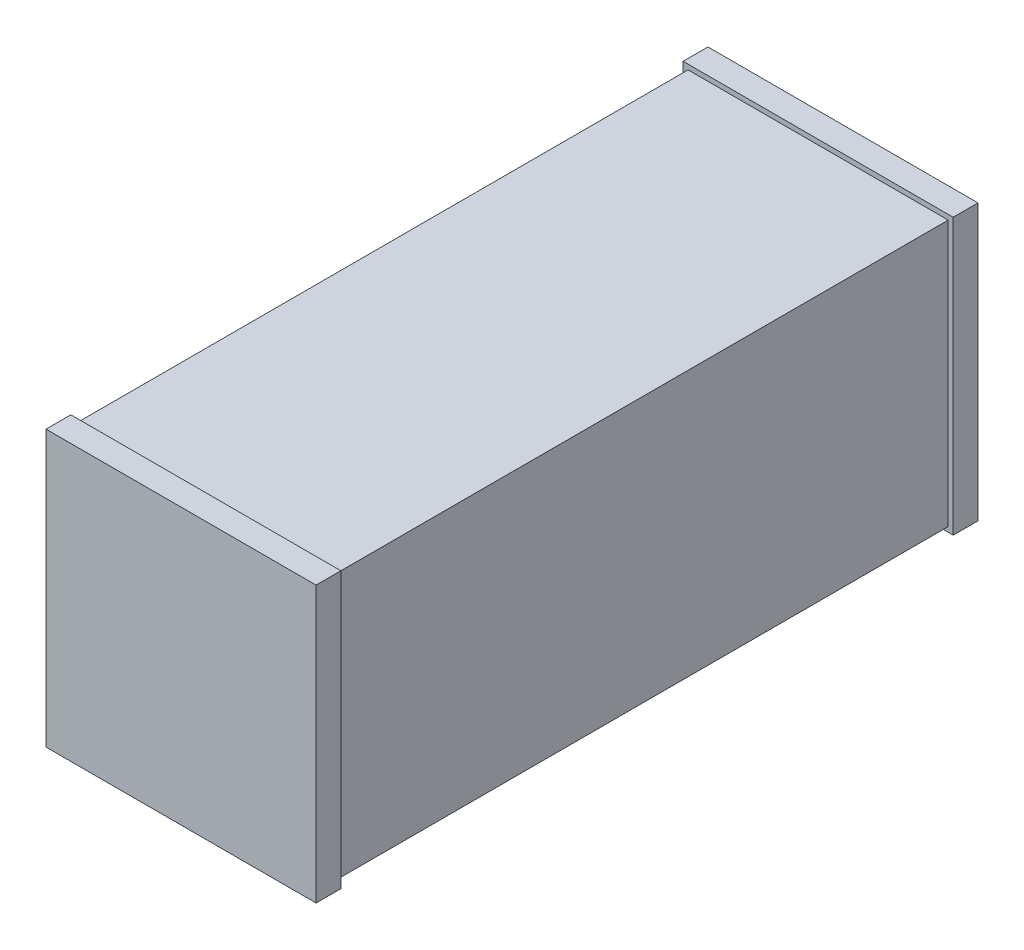
SolidWorks part; units mm, degrees
ref_plane "Front Plane" through (0, 0, 0) normal (0, 0, 1) x (1, 0, 0)
ref_plane "Top Plane" through (0, 0, 0) normal (0, 1, 0) x (1, 0, 0)
ref_plane "Right Plane" through (0, 0, 0) normal (1, 0, 0) x (0, 0, -1)
sketch "Sketch1" plane through (0, 0, 0) normal (0, 0, 1) x (1, 0, 0)
  line L1 (0, 0) -> (103.632, 0)
  line L2 (0, 0) -> (0, -105.664)
  line L3 (0, -105.664) -> (103.632, -105.664)
  line L4 (103.632, 0) -> (103.632, -105.664)
  dimension "D1" = 103.632
  dimension "D2" = 105.664
extrude "Boss-Extrude1" add sketch "Sketch1" against normal blind 9.525
sketch "Sketch2" plane through (0, 0, -9.525) normal (0, 0, -1) x (-1, 0, 0)
  line L0 (-103.632, 0) -> (0, 0) construction
  line L1 (-101.727, -1.905) -> (-1.905, -1.905)
  line L2 (-101.727, -1.905) -> (-101.727, -103.759)
  line L3 (-101.727, -103.759) -> (-1.905, -103.759)
  line L4 (-1.905, -1.905) -> (-1.905, -103.759)
  line L5 (-103.632, -105.664) -> (-103.632, 0) construction
  line L6 (0, 0) -> (0, -105.664) construction
  line L7 (0, -105.664) -> (-103.632, -105.664) construction
  dimension "D1" = 1.905
  dimension "D2" = 1.905
  dimension "D3" = 1.905
  dimension "D4" = 1.905
extrude "Boss-Extrude2" add sketch "Sketch2" along normal blind 234.95
sketch "Sketch4" plane through (0, 0, -244.475) normal (0, 0, -1) x (-1, 0, 0)
  line L8 (0, 0) -> (-103.632, 0)
  line L9 (-103.632, 0) -> (-103.632, -105.664)
  line L10 (-103.632, -105.664) -> (0, -105.664)
  line L11 (0, -105.664) -> (0, 0)
  line L12 (0, 0) -> (-103.632, 0)
  line L13 (-103.632, 0) -> (-103.632, -105.664)
  line L14 (-103.632, -105.664) -> (0, -105.664)
  line L15 (0, -105.664) -> (0, 0)
  dimension "D1" = 0
extrude "Boss-Extrude5" add sketch "Sketch4" along normal blind 9.525
sketch "Sketch5" plane through (0, -103.759, 0) normal (0, -1, 0) x (1, 0, 0)
  line L0 (101.727, -9.525) -> (1.905, -9.525) construction
  line L2 (15.3035, -19.05) -> (1.905, -19.05) construction
  line L3 (1.905, -244.475) -> (1.905, -9.525) construction
  line L4 (88.3285, -19.05) -> (101.727, -19.05) construction
  line L5 (101.727, -244.475) -> (101.727, -9.525) construction
  line L6 (15.3035, -234.95) -> (1.905, -234.95) construction
  line L7 (88.3285, -234.95) -> (101.727, -234.95) construction
  point P0 (15.3035, -19.05)
  point P1 (88.3285, -19.05)
  point P2 (15.3035, -234.95)
  point P3 (88.3285, -234.95)
  point P18 (0, 0)
  dimension "D1" = 73.025
  dimension "D2" = 215.9
  dimension "D3" = 9.525
hole_wizard "Tap Drill for #6-32 Tap1" positions "Sketch6" profile "Sketch7" hole size "#6-32" standard "ANSI Inch"
sketch "Sketch6" plane through (0, -103.759, 0) normal (0, -1, 0) x (-1, 0, 0)
  point P0 (-88.3285, 234.95)
  point P3 (-15.3035, 234.95)
  point P6 (-88.3285, 19.05)
  point P9 (-15.3035, 19.05)
sketch "Sketch7" plane through (88.3285, -103.759, -234.95) normal (1, 0, 0) x (0, 0, -1)
  line L0 (0, 0) -> (0, 4.7827)
  line L1 (0, 4.7827) -> (1.3525, 3.97)
  line L2 (1.3525, 3.97) -> (1.3525, 0)
  line L5 (1.3525, 0) -> (0, 0)
  line L10 (0, 4.7827) -> (-1.3526, 3.97) construction
  line L11 (0, -6.35) -> (0, 107.95) construction
  dimension "Hole Dia." = 2.7051
  dimension "Hole Depth" = 3.97
  dimension "Drill Angle" = 118
